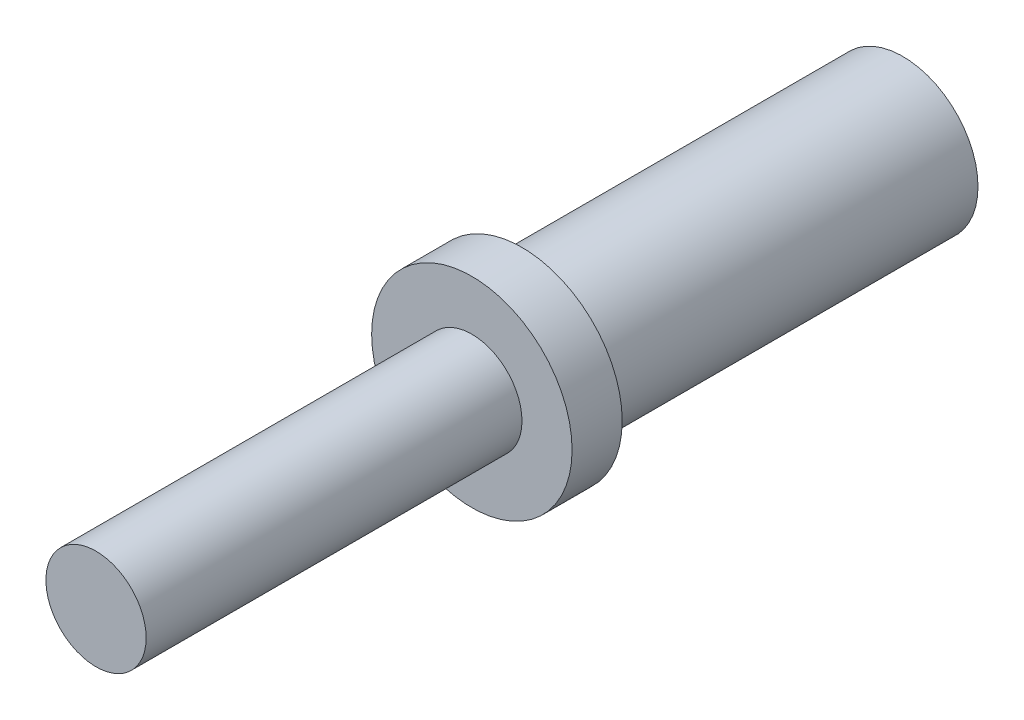
SolidWorks part; units mm, degrees
ref_plane "Front Plane" through (0, 0, 0) normal (0, 0, 1) x (1, 0, 0)
ref_plane "Top Plane" through (0, 0, 0) normal (0, 1, 0) x (1, 0, 0)
ref_plane "Right Plane" through (0, 0, 0) normal (1, 0, 0) x (0, 0, -1)
sketch "Sketch1" plane through (0, 0, 0) normal (1, 0, 0) x (0, 0, -1)
  line L0 (0, 0) -> (32.2, 0)
  line L1 (0, 0) -> (0, -2)
  line L2 (0, -2) -> (15, -2)
  line L3 (15, -2) -> (15, -4)
  line L4 (15, -4) -> (17, -4)
  line L5 (17, -4) -> (17, -3)
  line L6 (17, -3) -> (32.2, -3)
  line L7 (32.2, -3) -> (32.2, 0)
  point P8 (1.146, -2.2619)
  point P10 (35.7079, -3)
  point P11 (0, 0)
  dimension "D1" = 32.2
  dimension "D2" = 2
  dimension "D3" = 15
  dimension "D4" = 2
  dimension "D5" = 1
  dimension "D6" = 2
revolve "Revolve1" add sketch "Sketch1" angle 360 about L0
